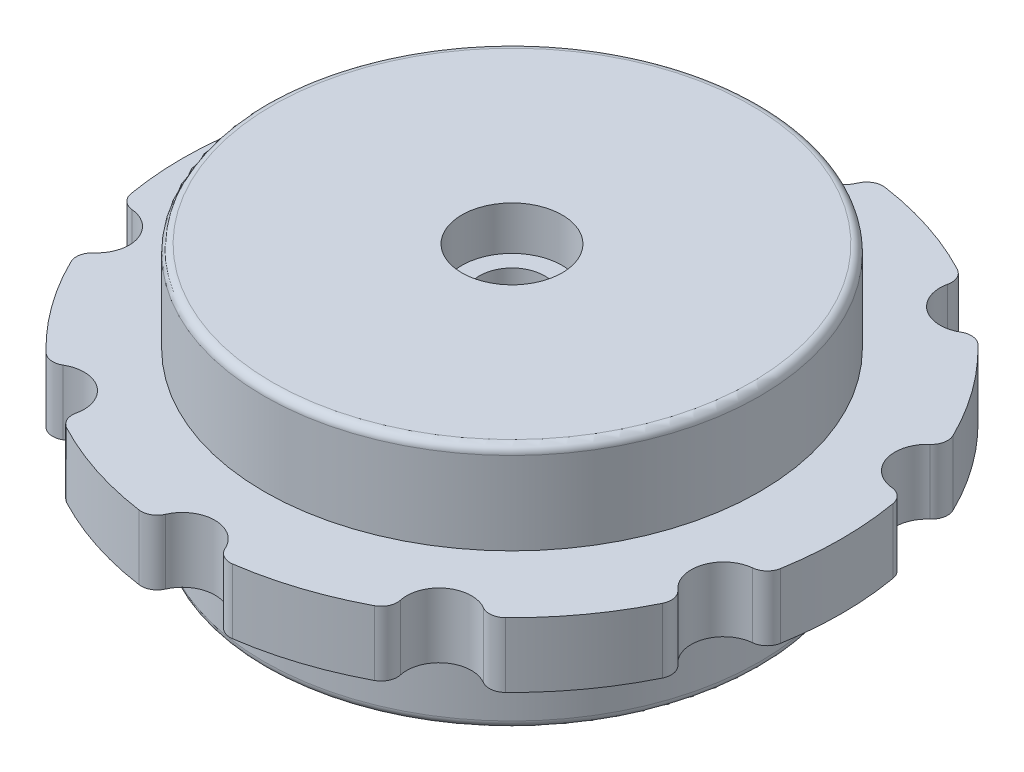
SolidWorks part; units mm, degrees
ref_plane "前视基准面" through (0, 0, 0) normal (0, 0, 1) x (1, 0, 0)
ref_plane "上视基准面" through (0, 0, 0) normal (0, 1, 0) x (1, 0, 0)
ref_plane "右视基准面" through (0, 0, 0) normal (1, 0, 0) x (0, 0, -1)
other "Configuration Table"
sketch "草图1" plane through (0, 0, 0) normal (0, 1, 0) x (1, 0, 0)
  circle A0 centre (0, 0) radius 15.3
  circle A1 centre (0, 0) radius 20.35
  circle A2 centre (0, 0) radius 13.7
  circle A3 centre (0, 20.35) radius 2
  dimension "D1" = 30.6
  dimension "D2" = 40.7
  dimension "D3" = 1.6
  dimension "D4" = 4
extrude "凸台-拉伸1" add sketch "草图1" along normal mid plane 15.2 contours A0 | A2
extrude "凸台-拉伸2" add sketch "草图1<3>" along normal mid plane 4 contours A1
sketch "草图1<3>" plane through (0, 0, 0) normal (0, 1, 0) x (1, 0, 0) same geometry as "草图1"
extrude "切除-拉伸1" cut sketch "草图1<4>" against normal through all both and the other way through all contours A3
sketch "草图1<4>" plane through (0, 0, 0) normal (0, 1, 0) x (1, 0, 0) same geometry as "草图1"
fillet "圆角1" radius 1 2 edges at (1.9976, 0, -20.2517) (-1.9976, 0, -20.2517)
pattern_circular "阵列(圆周)1" count 10 over 360 about axis through (0, 2, 0) along (0, -1, 0) of "切除-拉伸1", "圆角1"
fillet "圆角2" radius 0.5 2 edges at (0, -7.6, 15.3) (0, 7.6, 15.3)
extrude "凸台-拉伸3" add sketch "草图1<5>" along normal mid plane 7.8 contours A2
sketch "草图1<5>" plane through (0, 0, 0) normal (0, 1, 0) x (1, 0, 0) same geometry as "草图1"
extrude "凸台-拉伸5" add sketch "草图1<6>" along normal up to surface (7.6 mm away) from surface contours A2 up to face at (0, 7.6, 14.8) starting at face at (0, -7.6, 14.8)
sketch "草图1<6>" plane through (0, 0, 0) normal (0, 1, 0) x (1, 0, 0) same geometry as "草图1"
sketch "草图2" plane through (0, 2, 0) normal (0, 1, 0) x (1, 0, 0)
  line L0 (0, 20.35) -> (11.9614, 16.4635)
  line L1 (-11.9614, 16.4635) -> (0, 20.35)
  arc A0 (-1.834, 19.5523) -> (1.834, 19.5523) centre (0, 20.35) ccw construction
  arc A1 (10.0088, 16.8962) -> (12.9763, 14.7401) centre (11.9614, 16.4635) ccw construction
  arc A2 (-12.9763, 14.7401) -> (-10.0088, 16.8962) centre (-11.9614, 16.4635) ccw construction
  dimension "D1" = 12.577
  dimension "D2" = 12.577
sketch "草图4" plane through (0, -7.6, 0) normal (0, -1, 0) x (1, 0, 0)
  circle A0 centre (0, 0) radius 2
  circle A1 centre (0, 0) radius 3.1
  dimension "D1" = 4
  dimension "D2" = 6.2
extrude "切除-拉伸3" cut sketch "草图4" against normal through all contours A0
extrude "切除-拉伸4" cut sketch "草图4<3>" against normal blind 2.7 contours A1
sketch "草图4<3>" plane through (0, -7.6, 0) normal (0, -1, 0) x (1, 0, 0) same geometry as "草图4"
extrude "切除-拉伸5" cut sketch "草图4<4>" along normal blind 2.7 from surface contours A1 starting at face at (0, 7.6, -2)
sketch "草图4<4>" plane through (0, -7.6, 0) normal (0, -1, 0) x (1, 0, 0) same geometry as "草图4"
sketch "草图5" plane through (0, -7.6, 0) normal (0, -1, 0) x (1, 0, 0)
  circle A0 centre (0, 0) radius 13
  dimension "D1" = 26
extrude "切除-拉伸6" cut sketch "草图5" against normal blind 4.5
sketch "草图6" plane through (0, -3.1, 0) normal (0, -1, 0) x (1, 0, 0)
  circle A0 centre (0, 0) radius 2.75
  dimension "D1" = 5.5
extrude "切除-拉伸7" cut sketch "草图6" against normal blind 2
sketch "草图7" plane through (0, -3.1, 0) normal (0, -1, 0) x (1, 0, 0)
  circle A0 centre (-10, 0) radius 0.35
  circle A1 centre (5, 8.6603) radius 0.35
  circle A2 centre (5, -8.6603) radius 0.35
  point P9 (0, 0)
  dimension "D1" = 0.7
  dimension "D2" = 10
  dimension "D3" = 3
extrude "切除-拉伸8" cut sketch "草图7" against normal blind 5 contours A0 | A1 | A2
